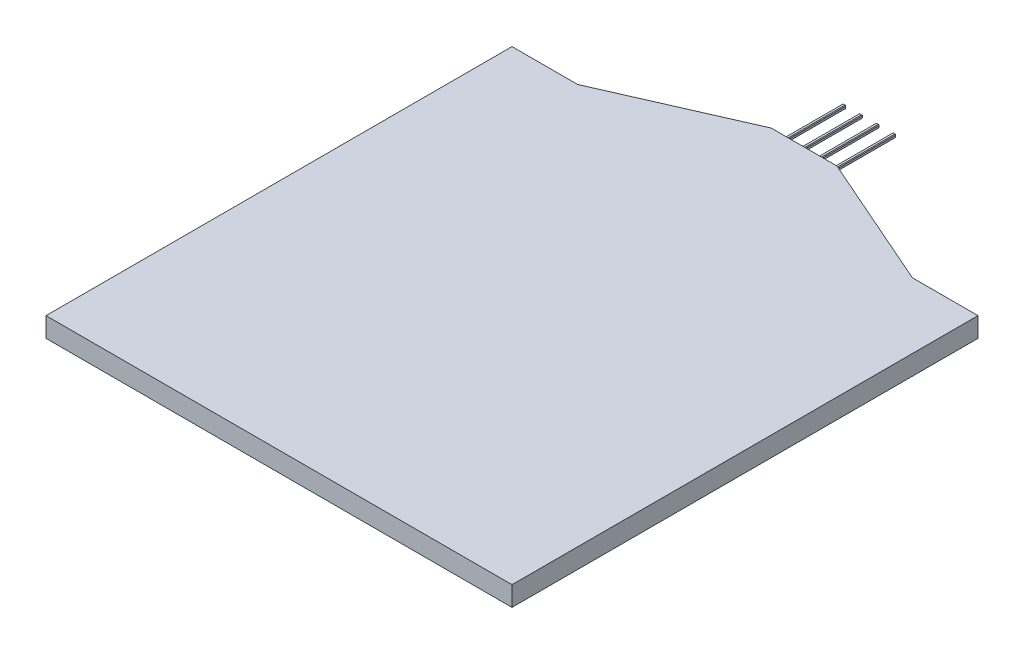
SolidWorks part; units mm, degrees
ref_plane "Front Plane" through (0, 0, 0) normal (0, 0, 1) x (1, 0, 0)
ref_plane "Top Plane" through (0, 0, 0) normal (0, 1, 0) x (1, 0, 0)
ref_plane "Right Plane" through (0, 0, 0) normal (1, 0, 0) x (0, 0, -1)
sketch "Sketch1" plane through (0, 0, 0) normal (0, 1, 0) x (1, 0, 0)
  line L0 (-35.5, 35.5) -> (-25.5, 35.5)
  line L1 (-35.5, 35.5) -> (35.5, 35.5)
  line L2 (-35.5, 35.5) -> (-35.5, -35.5)
  line L3 (-35.5, -35.5) -> (35.5, -35.5)
  line L4 (35.5, 35.5) -> (35.5, -35.5)
  line L5 (-25.5, 35.5) -> (-5, 44.5)
  line L6 (-5, 44.5) -> (5, 44.5)
  line L7 (5, 44.5) -> (25.5, 35.5)
  line L8 (25.5, 35.5) -> (35.5, 35.5)
  point P4 (-35.5, 0)
  point P6 (0, -35.5)
  point P11 (0, 44.5)
  point P12 (0, 35.5)
  dimension "D1" = 71
  dimension "D2" = 71
  dimension "D3" = 10
  dimension "D4" = 80
  dimension "D5" = 10
  dimension "D6" = 10
extrude "Boss-Extrude1" add sketch "Sketch1" along normal blind 3 contours L7 L6 L5 L1 | L4 L1 L0 L2 L3 region at (0, 0, 0) region at (0, 0, -38.9918)
sketch "Sketch2" plane through (0, 0, -44.5) normal (0, 0, -1) x (-1, 0, 0)
  line L0 (-5, 1.5) -> (5, 1.5) construction
  line L1 (-5, 3) -> (-5, 0) construction
  line L2 (5, 3) -> (5, 0) construction
  line L3 (0, 0) -> (-1.27, 1.5) construction
  line L4 (-4.06, 1.75) -> (-3.56, 1.75)
  line L5 (-4.06, 1.75) -> (-4.06, 1.25)
  line L6 (-4.06, 1.25) -> (-3.56, 1.25)
  line L7 (-3.56, 1.75) -> (-3.56, 1.25)
  line L8 (-4.06, 1.75) -> (-3.56, 1.25) construction
  line L9 (-4.06, 1.25) -> (-3.56, 1.75) construction
  line L10 (-1.52, 1.75) -> (-1.02, 1.75)
  line L11 (-1.52, 1.75) -> (-1.52, 1.25)
  line L12 (-1.52, 1.25) -> (-1.02, 1.25)
  line L13 (-1.02, 1.75) -> (-1.02, 1.25)
  line L14 (-1.52, 1.75) -> (-1.02, 1.25) construction
  line L15 (-1.52, 1.25) -> (-1.02, 1.75) construction
  line L16 (1.02, 1.75) -> (1.52, 1.75)
  line L17 (1.02, 1.75) -> (1.02, 1.25)
  line L18 (1.02, 1.25) -> (1.52, 1.25)
  line L19 (1.52, 1.75) -> (1.52, 1.25)
  line L20 (1.02, 1.75) -> (1.52, 1.25) construction
  line L21 (1.02, 1.25) -> (1.52, 1.75) construction
  line L22 (3.56, 1.75) -> (4.06, 1.75)
  line L23 (3.56, 1.75) -> (3.56, 1.25)
  line L24 (3.56, 1.25) -> (4.06, 1.25)
  line L25 (4.06, 1.75) -> (4.06, 1.25)
  line L26 (3.56, 1.75) -> (4.06, 1.25) construction
  line L27 (3.56, 1.25) -> (4.06, 1.75) construction
  line L28 (0, 0) -> (1.27, 1.5) construction
  line L29 (1.27, 1.5) -> (-1.27, 1.5) construction
  point P6 (-3.81, 1.5)
  point P11 (-1.27, 1.5)
  point P16 (1.27, 1.5)
  point P21 (3.81, 1.5)
  dimension "D1" = 0.5
  dimension "D2" = 0.5
  dimension "D3" = 0.5
  dimension "D4" = 0.5
  dimension "D5" = 0.5
  dimension "D6" = 0.5
  dimension "D7" = 0.5
  dimension "D8" = 0.5
  dimension "D9" = 2.54
  dimension "D10" = 2.54
  dimension "D11" = 2.54
extrude "Boss-Extrude2" add sketch "Sketch2" along normal blind 10
chamfer "Chamfer1" distance 0.1 angle 45 48 edges at (-4.06, 1.5, -44.5) (-4.06, 1.25, -49.5) (-3.81, 1.25, -44.5) (-3.81, 1.25, -54.5) (-4.06, 1.5, -54.5) (-4.06, 1.75, -49.5) (-3.81, 1.75, -54.5) (-3.81, 1.75, -44.5) (-3.56, 1.75, -49.5) (-3.56, 1.5, -54.5) (-3.56, 1.25, -49.5) (-3.56, 1.5, -44.5) (-1.02, 1.5, -44.5) (-1.02, 1.75, -49.5) (-1.27, 1.75, -44.5) (-1.52, 1.75, -49.5) (-1.52, 1.5, -44.5) (-1.02, 1.25, -49.5) (-1.27, 1.25, -44.5) (-1.52, 1.25, -49.5) (-1.27, 1.25, -54.5) (-1.02, 1.5, -54.5) (-1.27, 1.75, -54.5) (-1.52, 1.5, -54.5) (1.27, 1.25, -44.5) (1.02, 1.25, -49.5) (1.02, 1.5, -44.5) (1.27, 1.25, -54.5) (1.02, 1.5, -54.5) (1.02, 1.75, -49.5) (1.27, 1.75, -54.5) (1.27, 1.75, -44.5) (1.52, 1.75, -49.5) (1.52, 1.5, -54.5) (1.52, 1.25, -49.5) (1.52, 1.5, -44.5) (3.81, 1.75, -44.5) (3.81, 1.75, -54.5) (4.06, 1.75, -49.5) (4.06, 1.5, -54.5) (4.06, 1.5, -44.5) (4.06, 1.25, -49.5) (3.81, 1.25, -54.5) (3.81, 1.25, -44.5) (3.56, 1.25, -49.5) (3.56, 1.5, -54.5) (3.56, 1.75, -49.5) (3.56, 1.5, -44.5)
